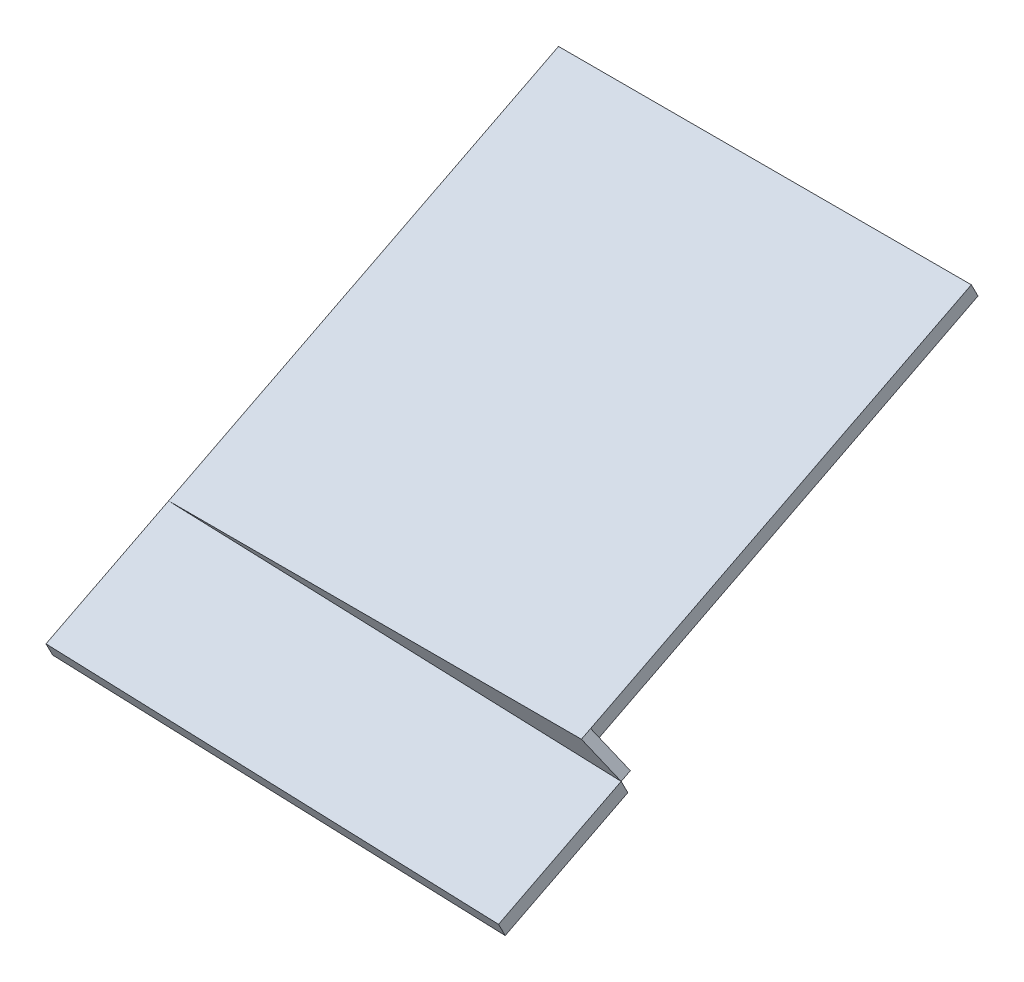
SolidWorks part; units mm, degrees
ref_plane "Front Plane" through (0, 0, 0) normal (0, 0, 1) x (1, 0, 0)
ref_plane "Top Plane" through (0, 0, 0) normal (0, 1, 0) x (1, 0, 0)
ref_plane "Right Plane" through (0, 0, 0) normal (1, 0, 0) x (0, 0, -1)
sketch "Sketch1" plane through (0, 0, 0) normal (1, 0, 0) x (0, 0, -1)
  line L0 (0, 0) -> (1106.541, 563.8108)
  line L1 (0, 0) -> (-19.3854, 38.046)
  line L2 (-19.3854, 38.046) -> (1087.1556, 601.8568)
  line L3 (1106.541, 563.8108) -> (1087.1556, 601.8568)
  dimension "D1" = 1241.9
  dimension "D2" = 42.7
extrude "Boss-Extrude1" add sketch "Sketch1" along normal blind 1200
ref_plane "Plane1" through (0, -13.6197, 26.7302) normal (0, -0.454, 0.891) x (1, 0, 0)
sketch "Sketch3" plane through (0, -13.6197, 26.7302) normal (0, -0.454, 0.891) x (1, 0, 0)
  line L0 (0, 42.7) -> (1265.1673, -67.9878)
  line L1 (0, 42.7) -> (0, 0)
  line L2 (0, 0) -> (1265.1673, -110.6878)
  line L3 (0, 42.7) -> (556.2794, 42.7)
  line L4 (1265.1673, -67.9878) -> (1265.1673, -110.6878)
  line L5 (0, 42.7) -> (1200, 42.7)
  line L6 (1200, 42.7) -> (1265.1673, -67.9878)
  line L7 (0, 42.7) -> (1265.1673, -67.9878)
  dimension "D1" = 1270
  dimension "D2" = 5
  dimension "D3" = 5
extrude "Boss-Extrude2" add sketch "Sketch3" along normal blind 400 separate body contours L4 L0 L1 L2 region at (632.5836, -43.9085, 11.2973)
extrude "Boss-Extrude3" add sketch "Sketch3<3>" against normal blind 30 contours L6 L5 L3 L0 region at (821.7224, -8.4483, 29.3652)
sketch "Sketch3<3>" plane through (0, -13.6197, 26.7302) normal (0, -0.454, 0.891) x (1, 0, 0) same geometry as "Sketch3"
